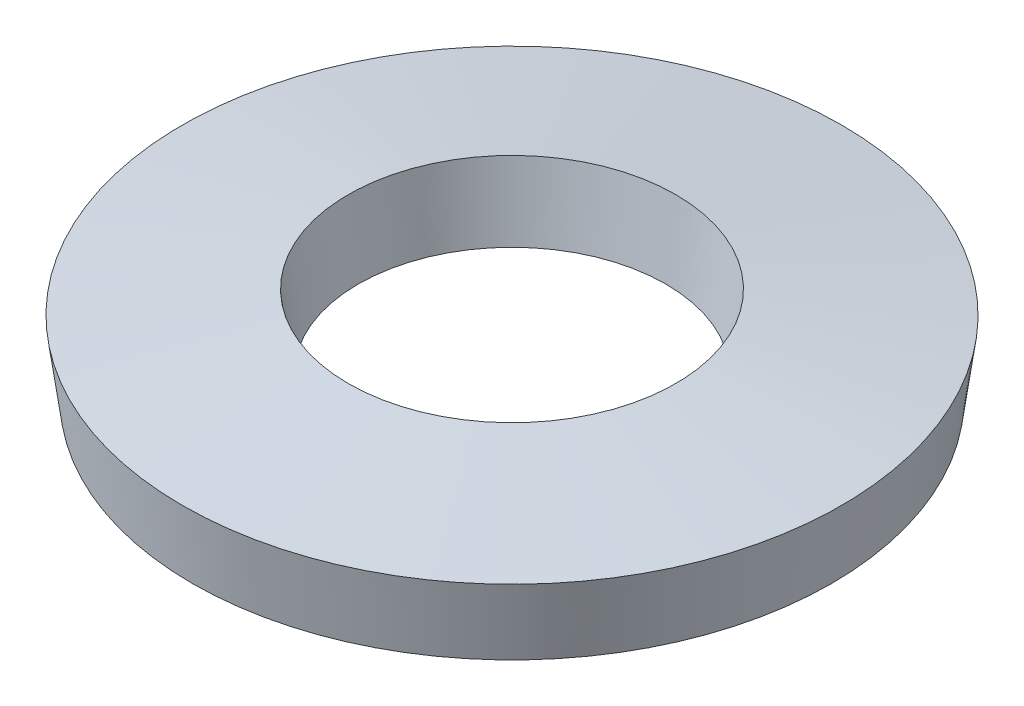
SolidWorks part; units mm, degrees
note: '?' marks a value the reader was unsure of.
ref_plane "Front" through (0, 0, 0) normal (0, 0, 1) x (1, 0, 0)
ref_plane "Top" through (0, 0, 0) normal (0, 1, 0) x (1, 0, 0)
ref_plane "Right" through (0, 0, 0) normal (1, 0, 0) x (0, 0, -1)
sketch "Sketch1" plane through (0, 0, 0) normal (0, 0, 1) x (1, 0, 0)
  line L0 (8.7295, 0) -> (4.2, 0.6184)
  line L1 (4.2, 0.6184) -> (4.4705, 2.6)
  line L2 (4.4705, 2.6) -> (9, 1.9816)
  line L3 (9, 1.9816) -> (8.7295, 0)
  line L4 (0, 0) -> (0, 2.6) construction
  line L5 (-9, 1.9816) -> (-8.7295, 0) construction
  line L6 (-4.4705, 2.6) -> (-9, 1.9816) construction
  line L7 (-4.2, 0.6184) -> (-4.4705, 2.6) construction
  line L8 (-8.7295, 0) -> (-4.2, 0.6184) construction
  point P5 (4.3353, 1.6092)
  point P8 (-4.3353, 1.6092)
  dimension "ID" = 8.4
  dimension "Thickness" = 2
  dimension "D1" = 4.5715
revolve "Revolve1" add sketch "Sketch1" angle 360 about L4
sketch "Sketch15" plane through (0, 0, 0) normal (0, 1, 0) x (1, 0, 0)
  circle A0 centre (0, 0) radius 9
  circle A1 centre (0, 0) radius 4.2
ref_plane "Plane10" through (0, 2.6, 0) normal (0, 1, 0) x (-1, 0, 0)
surface "Surface-Knit1"
surface "Surface-Extend1" [suppressed] parameters "D1"=1.27, "D2"=1.27
sketch "Sketch13" plane through (0, 2.6, 0) normal (0, 1, 0) x (-1, 0, 0)
  line L0 (-9.1263, 2.171) -> (-3.8064, -0.3097)
  line L2 (-8.7295, 0) -> (-4.2, 0) construction
  circle A3 centre (0, 0) radius 3.819
  circle A4 centre (0, 0) radius 3.819 construction
  circle A6 centre (0, 0) radius 9.381
  circle A7 centre (0, 0) radius 9.381 construction
  dimension "D1" = 25
  dimension "D2" = 0.381
  dimension "D3" = 0.381
extrude "Cut-Extrude-Thin12" [suppressed] cut sketch "Sketch13" against normal offset from surface (0.3134 mm away) 0.25 thin
surface "Surface-Knit2"
surface "Surface-Extend2" parameters "D1"=0.762, "D2"=0.762
sketch "Sketch14" plane through (0, 0, 0) normal (0, 1, 0) x (1, 0, 0)
  line L0 (9.1263, -2.171) -> (3.8064, 0.3097) construction
  line L1 (9.1263, -2.171) -> (3.8064, 0.3097)
extrude "Cut-Extrude-Thin13" [suppressed] cut sketch "Sketch14" along normal offset from surface (0.0096 mm away) 0.25 thin
chamfer "Chamfer1" [suppressed] distance 0.225 angle 45
pattern_circular "CirPattern3" [suppressed] count 24 over 360
delete or keep bodies "Body-Delete1" type delete bodies bodies 120
delete or keep bodies "Body-Delete2" type delete bodies bodies 119
ref_axis "Center Axis 1" through (0, 0.63, 0) along (0, -1, 0)?
equation "\"D1@Cut-Extrude-Thin12\" = \"Thickness@Sketch1\"*.125"
equation "\"D1@Cut-Extrude-Thin13\" = \"D1@Cut-Extrude-Thin12\""
equation "\"D1@Chamfer1\" = \"D1@Cut-Extrude-Thin12\"*.9"
